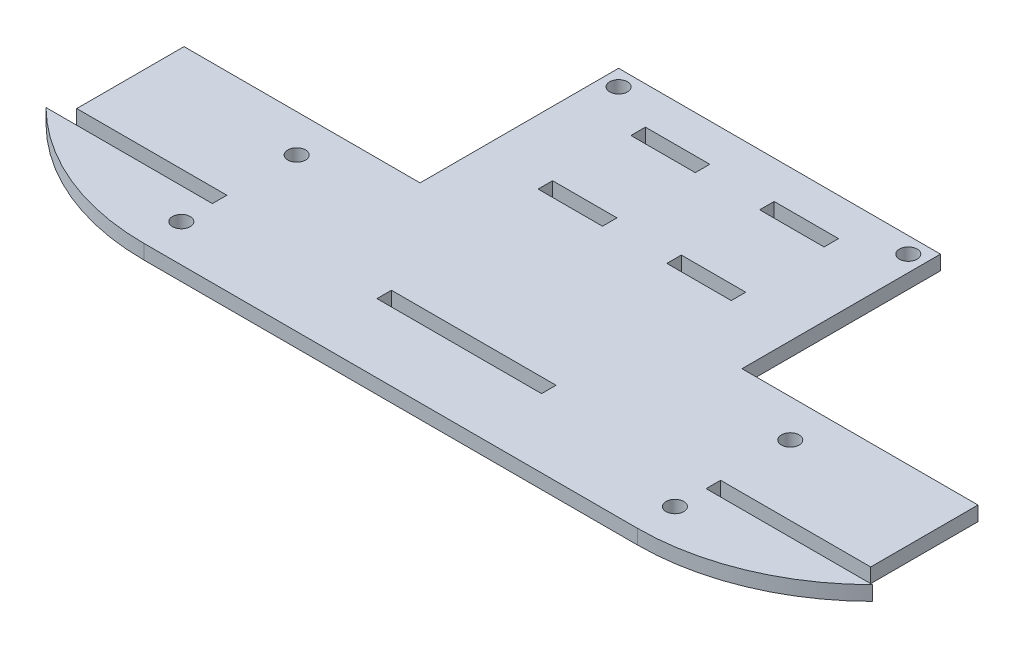
SolidWorks part; units mm, degrees
ref_plane "Ön Düzlem" through (0, 0, 0) normal (0, 0, 1) x (1, 0, 0)
ref_plane "Üst Düzlem" through (0, 0, 0) normal (0, 1, 0) x (1, 0, 0)
ref_plane "Sağ Düzlem" through (0, 0, 0) normal (1, 0, 0) x (0, 0, -1)
sketch "Sketch1" plane through (0, 0, 0) normal (0, 1, 0) x (1, 0, 0)
  line L1 (-46, 0) -> (46, 0)
  line L19 (-73.9952, 35.5) -> (-73.9952, 15.5)
  line L21 (73.9952, 35.5) -> (73.9952, 15.5)
  line L22 (-15.34, 15.5) -> (-15.34, 12.8)
  line L23 (-46.0152, 15.5) -> (-46.0152, 12.8)
  line L24 (-15.34, 12.8) -> (15.34, 12.8)
  line L25 (15.34, 12.8) -> (15.34, 15.5)
  line L26 (15.34, 15.5) -> (-15.34, 15.5)
  line L29 (46.0152, 15.5) -> (46.0152, 12.8)
  line L31 (46.0152, 15.5) -> (73.9952, 15.5)
  line L32 (77.0252, 12.8) -> (46.0152, 12.8)
  line L33 (-46.0152, 15.5) -> (-73.9952, 15.5)
  line L34 (-46.0152, 12.8) -> (-77.0252, 12.8)
  line L55 (-30, 70.5) -> (-30, 72.5)
  line L56 (73.9952, 35.5) -> (30, 35.5)
  line L57 (18, 45.5) -> (6, 45.5)
  line L59 (-6, 62.8) -> (-18, 62.8)
  line L60 (6, 45.5) -> (6, 48.2)
  line L61 (18, 62.8) -> (6, 62.8)
  line L63 (-6, 65.5) -> (-6, 62.8)
  line L64 (-6, 65.5) -> (-18, 65.5)
  line L65 (-6, 48.2) -> (-18, 48.2)
  line L66 (18, 65.5) -> (6, 65.5)
  line L67 (-6, 45.5) -> (-18, 45.5)
  line L68 (18, 48.2) -> (6, 48.2)
  line L71 (-18, 45.5) -> (-18, 48.2)
  line L72 (6, 65.5) -> (6, 62.8)
  line L73 (-18, 65.5) -> (-18, 62.8)
  line L74 (-6, 45.5) -> (-6, 48.2)
  line L75 (30, 70.5) -> (30, 35.5)
  line L76 (-30, 35.5) -> (-30, 70.5)
  line L77 (18, 45.5) -> (18, 48.2)
  line L78 (18, 65.5) -> (18, 62.8)
  line L79 (-30, 35.5) -> (-73.9952, 35.5)
  line L81 (-30, 72.5) -> (30, 72.5)
  line L82 (30, 72.5) -> (30, 70.5)
  arc A0 (-77.0252, 12.8) -> (-46, 0) centre (-46, 44) ccw
  arc A1 (46, 0) -> (77.0252, 12.8) centre (46, 44) ccw
  circle A2 centre (46, 28.5) radius 1.65
  circle A3 centre (46, 7) radius 1.65
  circle A4 centre (-46, 7) radius 1.65
  circle A5 centre (-46, 28.5) radius 1.65
  circle A6 centre (-27, 69.5) radius 1.65
  circle A7 centre (27, 69.5) radius 1.65
  point P52 (0, 50.5)
extrude "Boss-Extrude1" add sketch "Sketch1" along normal blind 2.7
